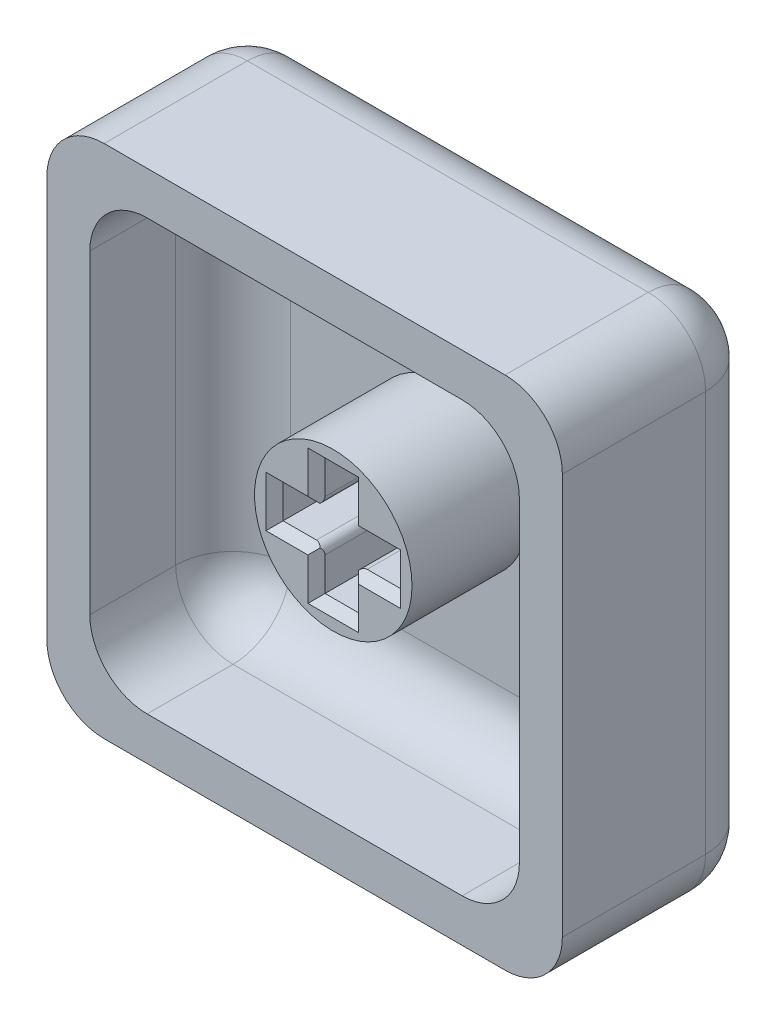
SolidWorks part; units mm, degrees
ref_plane "Front Plane" through (0, 0, 0) normal (0, 0, 1) x (1, 0, 0)
ref_plane "Top Plane" through (0, 0, 0) normal (0, 1, 0) x (1, 0, 0)
ref_plane "Right Plane" through (0, 0, 0) normal (1, 0, 0) x (0, 0, -1)
sketch "Sketch1" plane through (0, 0, 0) normal (0, 0, 1) x (1, 0, 0)
  line L1 (-9.525, 9.525) -> (9.525, 9.525)
  line L2 (-9.525, 9.525) -> (-9.525, -9.525)
  line L3 (-9.525, -9.525) -> (9.525, -9.525)
  line L4 (9.525, 9.525) -> (9.525, -9.525)
  line L5 (-9, 9) -> (9, 9)
  line L6 (-9, 9) -> (-9, -9)
  line L7 (-9, -9) -> (9, -9)
  line L8 (9, 9) -> (9, -9)
  line L9 (-0.585, 2.05) -> (0.585, 2.05)
  line L10 (-0.585, 2.05) -> (-0.585, -2.05)
  line L11 (-0.585, -2.05) -> (0.585, -2.05)
  line L12 (0.585, 2.05) -> (0.585, -2.05)
  line L13 (-2.05, 0.585) -> (2.05, 0.585)
  line L14 (-2.05, 0.585) -> (-2.05, -0.585)
  line L15 (-2.05, -0.585) -> (2.05, -0.585)
  line L16 (2.05, 0.585) -> (2.05, -0.585)
  line L17 (-7.5, 7.5) -> (7.5, 7.5)
  line L18 (-7.5, 7.5) -> (-7.5, -7.5)
  line L19 (-7.5, -7.5) -> (7.5, -7.5)
  line L20 (7.5, 7.5) -> (7.5, -7.5)
  circle A0 centre (0, 0) radius 2.75
  point P19 (-9.525, 0)
  point P20 (-9, 0)
  point P21 (-2.05, 0)
  point P22 (0, 9.525)
  point P23 (0, 9)
  point P24 (0, 2.05)
  point P25 (-0.585, 0)
  point P26 (0, -0.585)
  point P31 (-7.5, 0)
  point P32 (0, 7.5)
  dimension "D9" = 5.5
  dimension "D1" = 19.05
  dimension "D2" = 19.05
  dimension "D3" = 18
  dimension "D4" = 18
  dimension "D5" = 1.17
  dimension "D6" = 1.17
  dimension "D7" = 4.1
  dimension "D8" = 4.1
  dimension "D10" = 1.5
  dimension "D11" = 1.5
extrude "Boss-Extrude1" add sketch "Sketch1" against normal blind 2 contours L5 L8 L7 L6
extrude "Boss-Extrude2" add sketch "Sketch1<4>" along normal blind 4 contours A0 L13 L16 L15 L12 L11 L10 L14 L9 region at (-2.6722, 0, 0)
sketch "Sketch1<4>" plane through (0, 0, 0) normal (0, 0, 1) x (1, 0, 0) same geometry as "Sketch1"
extrude "Boss-Extrude3" add sketch "Sketch1<5>" along normal blind 5 contours L8 L5 L6 L7 L17 L20 L19 L18 region at (0, 8.7454, 0)
sketch "Sketch1<5>" plane through (0, 0, 0) normal (0, 0, 1) x (1, 0, 0) same geometry as "Sketch1"
chamfer "Chamfer1" distance 0.3 angle 45 12 edges at (2.05, 0, 4) (1.3175, 0.585, 4) (0.585, 1.3175, 4) (0, 2.05, 4) (1.3175, -0.585, 4) (0.585, -1.3175, 4) (0, -2.05, 4) (-0.585, -1.3175, 4) (-1.3175, -0.585, 4) (-2.05, 0, 4) (-1.3175, 0.585, 4) (-0.585, 1.3175, 4)
fillet "Fillet3" radius 0.3 4 edges at (0.585, -0.585, 1.85) (0.585, 0.585, 1.85) (-0.585, 0.585, 1.85) (-0.585, -0.585, 1.85)
fillet "Fillet4" radius 2 16 edges at (0, -9, -2) (-9, 0, -2) (0, 9, -2) (9, 0, -2) (9, -9, 1.5) (9, 9, 1.5) (-9, -9, 1.5) (-9, 9, 1.5) (0, -7.5, 0) (7.5, 0, 0) (0, 7.5, 0) (-7.5, 0, 0) (-7.5, 7.5, 2.5) (7.5, 7.5, 2.5) (7.5, -7.5, 2.5) (-7.5, -7.5, 2.5)
equation "\"max1u\"=19.05"
equation "\"D1@Sketch1\"=\"max1u\""
equation "\"D2@Sketch1\"=\"max1u\""
equation "\"keycap1u\"=18"
equation "\"D3@Sketch1\"=\"keycap1u\""
equation "\"D4@Sketch1\"=\"keycap1u\""
equation "\"stem\"=1.17"
equation "\"D5@Sketch1\"=\"stem\""
equation "\"D6@Sketch1\"=\"stem\""
equation "\"stemWidth\"=4.1"
equation "\"D7@Sketch1\"=\"stemWidth\""
equation "\"D8@Sketch1\"=\"stemWidth\""
equation "\"keycapWall\"= 1.5"
equation "\"D10@Sketch1\"=\"keycapWall\""
equation "\"D11@Sketch1\"=\"keycapWall\""
equation "\"stemRound\"=0.3"
equation "\"D1@Fillet1\"=\"stemRound\""
equation "\"D1@Chamfer1\"=\"stemRound\""
equation "\"exRound\"=2"
equation "\"D1@Fillet4\"=\"exRound\""
